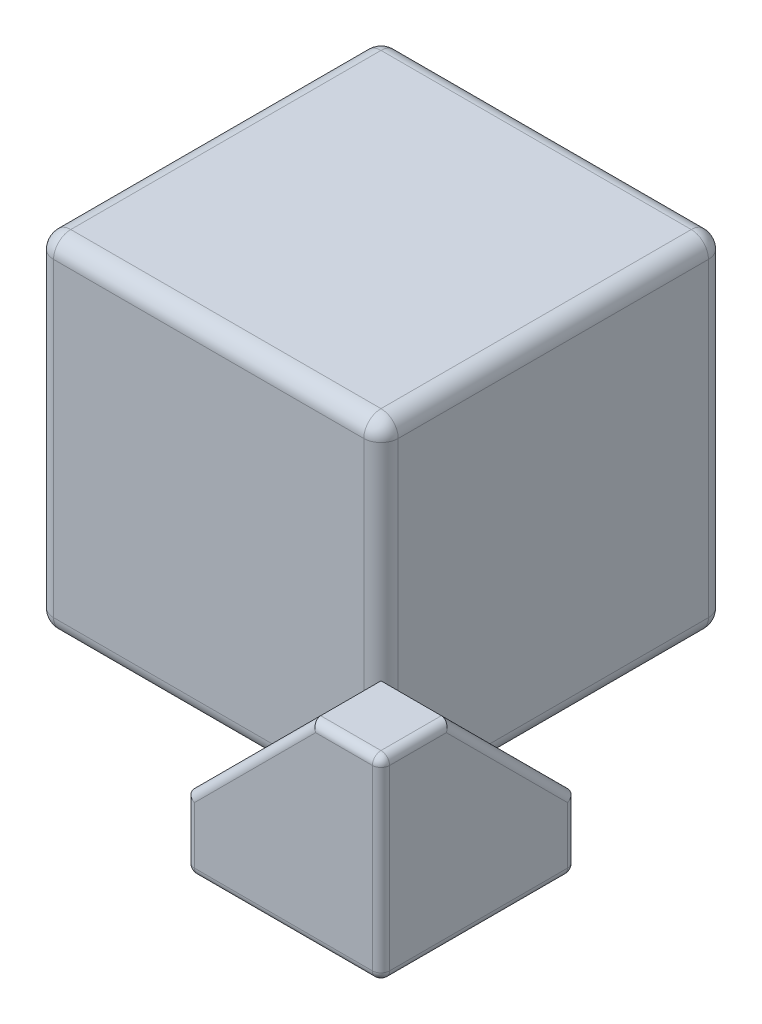
SolidWorks part; units mm, degrees
material "PS HI"
ref_plane "Ön Düzlem" through (0, 0, 0) normal (0, 0, 1) x (1, 0, 0)
ref_plane "Üst Düzlem" through (0, 0, 0) normal (0, 1, 0) x (1, 0, 0)
ref_plane "Sağ Düzlem" through (0, 0, 0) normal (1, 0, 0) x (0, 0, -1)
sketch "Çizim1" plane through (0, 0, 0) normal (0, 0, 1) x (1, 0, 0)
  line L1 (-10, -10) -> (10, -10)
  line L2 (-10, -10) -> (-10, 10)
  line L3 (-10, 10) -> (10, 10)
  line L4 (10, -10) -> (10, 10)
  line L5 (-10, -10) -> (10, 10) construction
  line L6 (-10, 10) -> (10, -10) construction
  point P0 (0, 0)
  dimension "D1" = 20
  dimension "D2" = 20
extrude "Yükseklik-Ekstrüzyon1" add sketch "Çizim1" along normal mid plane 20
shell "İç Boşaltma1" thickness 1 removed face at (0, -10, 0)
sketch "Çizim6" plane through (10, 0, 0) normal (1, 0, 0) x (0, 0, -1)
  line L0 (-10, -2.6795) -> (-2.6795, -10)
  line L1 (-10, -10) -> (-10, 10) construction
  line L2 (-10, -10) -> (10, -10) construction
  line L3 (-2.6795, -10) -> (-10, -10)
  line L4 (-10, -10) -> (-10, -2.6795)
  line L5 (-2.6795, -10) -> (-2.6795, -14)
  line L6 (-10, -2.6795) -> (-14, -2.6795)
  line L7 (-14, -2.6795) -> (-14, -14)
  line L8 (-14, -14) -> (-2.6795, -14)
  line M3 (-10, 10) -> (-10, -10)
  line M4 (-10, -10) -> (10, -10)
  dimension "D1" = 4
  dimension "D2" = 4
extrude "Yükseklik-Ekstrüzyon3" add sketch "Çizim6" along normal blind 4 contours L0 M3 M4 | L7 L8 L5 L6 M4 M3 region at (10, -7.5598, 7.5598) region at (10, -6.3397, 10.1601)
sketch "Çizim7" plane through (0, 0, 10) normal (0, 0, 1) x (1, 0, 0)
  line L0 (10, -2.6795) -> (2.6795, -10)
  line L1 (-10, -10) -> (10, -10) construction
  line L2 (2.6795, -10) -> (2.6795, -14)
  line L3 (2.6795, -30) -> (2.6795, -10) construction
  line L4 (2.6795, -14) -> (10, -14)
  line L5 (10, -14) -> (10, -2.6795)
extrude "Yükseklik-Ekstrüzyon4" add sketch "Çizim7" along normal blind 4
sketch "Çizim8" plane through (0, -14, 0) normal (0, -1, 0) x (1, 0, 0)
  line L0 (10, 2.6795) -> (2.6795, 10)
  line L1 (2.6795, 10) -> (10, 10)
  line L2 (10, 10) -> (10, 2.6795)
extrude "Yükseklik-Ekstrüzyon5" add sketch "Çizim8" against normal up to surface (23 mm away) up to face at (0, 9, 0)
fillet "Radyus1" radius 1 8 edges at (10, 3.6603, 10) (-10, 0, 10) (-10, 0, -10) (10, 0, -10) (-10, 10, 0) (0, 10, -10) (0, 10, 10) (10, 10, 0)
fillet "Radyus2" radius 1 7 edges at (-3.1603, -10, 10) (-9.7071, -10, 9.7071) (-10, -10, 0) (-9.7071, -10, -9.7071) (0, -10, -10) (9.7071, -10, -9.7071) (10, -10, -3.1603)
fillet "Radyus3" radius 0.5 12 edges at (14, -14, 8.3397) (12, -14, 2.6795) (6.3397, -14, 6.3397) (2.6795, -14, 12) (8.3397, -14, 14) (14, -12, 2.6795) (14, -6.3397, 6.3397) (14, -2.6795, 12) (14, -8.3397, 14) (2.6795, -12, 14) (12, -2.6795, 14) (6.3397, -6.3397, 14)
sketch "Çizim9" plane through (0, -14, 0) normal (0, -1, 0) x (1, 0, 0)
  line L0 (12.5, 4.1795) -> (12.5, 12.5)
  line L1 (12.5, 12.5) -> (4.1795, 12.5)
  line L2 (4.1795, 12.5) -> (4.1795, 10.6213)
  line L3 (4.1795, 10.6213) -> (10.6213, 4.1795)
  line L4 (10.6213, 4.1795) -> (12.5, 4.1795)
extrude "Kes-Ekstrüzyon1" cut sketch "Çizim9" against normal blind 3.5
